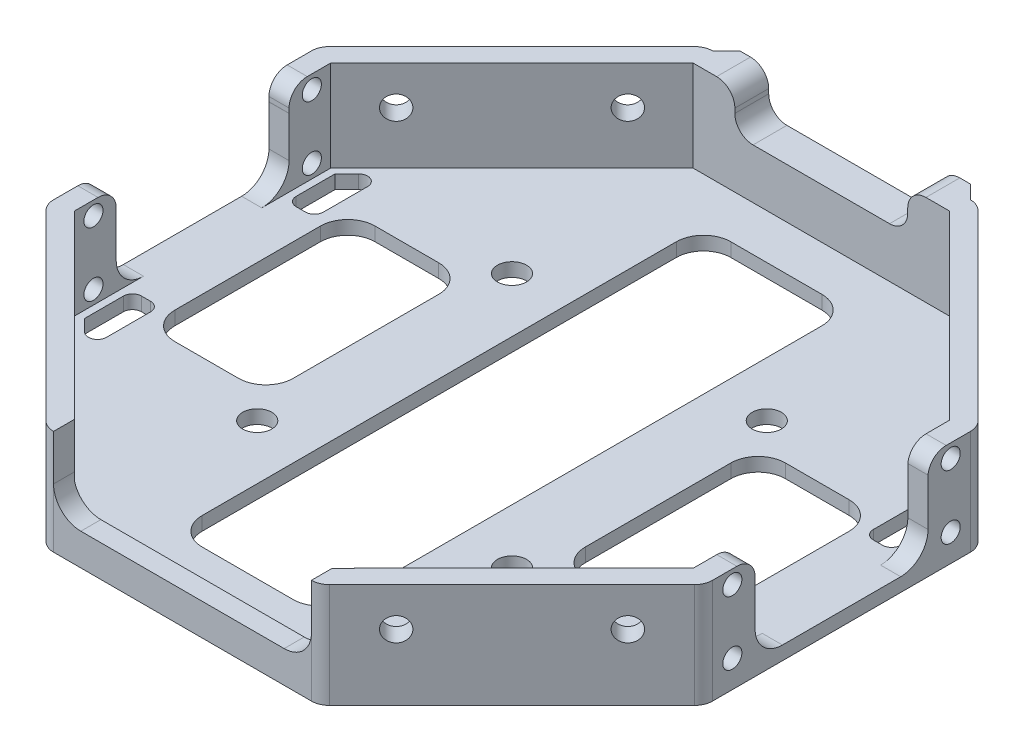
SolidWorks part; units mm, degrees
material "Tough 2000"
ref_plane "Front Plane" through (0, 0, 0) normal (0, 0, 1) x (1, 0, 0)
ref_plane "Top Plane" through (0, 0, 0) normal (0, 1, 0) x (1, 0, 0)
ref_plane "Right Plane" through (0, 0, 0) normal (1, 0, 0) x (0, 0, -1)
sketch "Sketch1" plane through (0, 0, 0) normal (0, 1, 0) x (1, 0, 0)
  line L1 (-11.2132, 40) -> (18.7868, 40)
  line L2 (18.7868, 40) -> (40, 18.7868)
  line L3 (40, 18.7868) -> (40, -11.2132)
  line L5 (-32.4264, 18.7868) -> (-32.4264, -11.2132)
  line L6 (-11.2132, 40) -> (-32.4264, 18.7868)
  line L7 (18.7868, -32.4264) -> (40, -11.2132)
  line L8 (-11.2132, -32.4264) -> (18.7868, -32.4264)
  line L9 (-11.2132, -32.4264) -> (-32.4264, -11.2132)
  point P13 (-32.4264, 3.7868)
  dimension "D1" = 30
  dimension "D2" = 30
  dimension "D3" = 40
  dimension "D4" = 40
extrude "Boss-Extrude1" add sketch "Sketch1" along normal blind 11.5
shell "Shell1" thickness 3 removed face at (3.7868, 11.5, -3.7868)
sketch "Sketch3" plane through (-21.8198, 0, 21.8198) normal (-0.7071, 0, 0.7071) x (0.7071, 0, 0.7071)
  line L0 (0, 11.5) -> (0, 7.25) construction
  line L1 (-15, 11.5) -> (15, 11.5) construction
  line L2 (0, 7.25) -> (9, 7.25) construction
  line L3 (0, 7.25) -> (-9, 7.25) construction
  circle A0 centre (-9, 7.25) radius 1.3
  circle A1 centre (9, 7.25) radius 1.3
extrude "Cut-Extrude1" cut sketch "Sketch3" against normal blind 94
sketch "Sketch4" plane through (-25.6066, 0, -25.6066) normal (-0.7071, 0, -0.7071) x (-0.7071, 0, 0.7071)
  line L0 (-5.3553, 11.5) -> (-5.3553, 7.25) construction
  line L1 (-20.3553, 11.5) -> (9.6447, 11.5) construction
  line L2 (-5.3553, 7.25) -> (-14.3553, 7.25) construction
  line L3 (-5.3553, 7.25) -> (3.6447, 7.25) construction
  circle A0 centre (-14.3553, 7.25) radius 1.3
  circle A1 centre (3.6447, 7.25) radius 1.3
extrude "Cut-Extrude2" cut sketch "Sketch4" against normal blind 94
fillet "Fillet1" radius 2 8 edges at (40, 5.75, 11.2132) (18.7868, 5.75, 32.4264) (40, 5.75, -18.7868) (18.7868, 5.75, -40) (-11.2132, 5.75, -40) (-32.4264, 5.75, -18.7868) (-32.4264, 5.75, 11.2132) (-11.2132, 5.75, 32.4264)
sketch "Sketch5" plane through (0, 0, 32.4264) normal (0, 0, 1) x (1, 0, 0)
  line L0 (3.7868, 11.5) -> (3.7868, 7) construction
  line L1 (-10.3848, 11.5) -> (17.9584, 11.5) construction
  line L2 (3.7868, 7) -> (13.2868, 7)
  line L3 (13.2868, 7) -> (13.2868, 11.5)
  line L4 (3.7868, 7) -> (-5.7132, 7)
  line L5 (-5.7132, 7) -> (-5.7132, 11.5)
  line L6 (-5.7132, 11.5) -> (13.2868, 11.5)
  dimension "D1" = 9.5
extrude "Cut-Extrude3" cut sketch "Sketch5" against normal blind 79
sketch "Sketch6" plane through (-32.4264, 0, 0) normal (-1, 0, 0) x (0, 0, 1)
  line L0 (-3.7868, 11.5) -> (-3.7868, 7) construction
  line L1 (-17.9584, 11.5) -> (10.3848, 11.5) construction
  line L2 (-3.7868, 7) -> (5.7132, 7)
  line L3 (5.7132, 7) -> (5.7132, 11.5)
  line L4 (-3.7868, 7) -> (-13.2868, 7)
  line L5 (-13.2868, 7) -> (-13.2868, 11.5)
  line L6 (-13.2868, 11.5) -> (5.7132, 11.5)
  dimension "D1" = 9.5
extrude "Cut-Extrude4" cut sketch "Sketch6" against normal blind 79
fillet "Fillet2" radius 2 16 edges at (38.5, 11.5, 5.7132) (38.5, 7, 5.7132) (38.5, 11.5, -13.2868) (38.5, 7, -13.2868) (13.2868, 11.5, 30.9264) (13.2868, 7, 30.9264) (-5.7132, 11.5, 30.9264) (-5.7132, 7, 30.9264) (-30.9264, 11.5, -13.2868) (-30.9264, 7, -13.2868) (-30.9264, 11.5, 5.7132) (-30.9264, 7, 5.7132) (13.2868, 11.5, -38.5) (13.2868, 7, -38.5) (-5.7132, 11.5, -38.5) (-5.7132, 7, -38.5)
sketch "Sketch8" plane through (40, 0, 0) normal (1, 0, 0) x (0, 0, -1)
  line L0 (3.7868, 7) -> (-8.2132, 7) construction
  line L1 (11.2868, 7) -> (-3.7132, 7) construction
  line L2 (-8.2132, 7) -> (-8.2132, 10) construction
  line L3 (-8.2132, 7) -> (-8.2132, 3) construction
  line L4 (3.7868, 7) -> (3.7868, 3) construction
  line L5 (15.7868, 7) -> (15.7868, 3) construction
  circle A0 centre (-8.2132, 10) radius 1.05
  circle A1 centre (-8.2132, 3) radius 1.05
  circle A2 centre (15.7868, 3) radius 1.05
  circle A3 centre (15.7868, 10) radius 1.05
extrude "Cut-Extrude7" cut sketch "Sketch8" against normal blind 79
sketch "Sketch10" plane through (0, 3, 0) normal (0, 1, 0) x (1, 0, 0)
  line L0 (17.5442, 37) -> (37, 17.5442)
  line L1 (37, 17.5442) -> (37, -9.9706)
  line L2 (37, -9.9706) -> (17.5442, -29.4264)
  line L3 (17.5442, -29.4264) -> (-9.9706, -29.4264)
  line L4 (-9.9706, -29.4264) -> (-29.4264, -9.9706)
  line L5 (-29.4264, -9.9706) -> (-29.4264, 17.5442)
  line L6 (-29.4264, 17.5442) -> (-9.9706, 37)
  line L7 (-9.9706, 37) -> (17.5442, 37)
extrude "Cut-Extrude8" cut sketch "Sketch10" against normal blind 1.5
sketch "Sketch12" plane through (0, 1.5, 0) normal (0, 1, 0) x (1, 0, 0)
  line L0 (-29.4264, 17.5442) -> (-26.4264, 20.5442)
  line L1 (-29.4264, -3.7132) -> (-29.4264, 11.2868) construction
  line L2 (-29.4264, -5.7132) -> (-29.4264, -3.7132) construction
  line L3 (-29.4264, -4.7132) -> (-26.4264, -4.7132)
  line L4 (-26.4264, -4.7132) -> (-26.4264, -12.9706)
  line L5 (-29.4264, -9.9706) -> (-9.9706, -29.4264) construction
  line L6 (-29.4264, -4.7132) -> (-29.4264, -9.9706)
  line L7 (-29.4264, -9.9706) -> (-26.4264, -12.9706)
  line L8 (3.7868, 37) -> (3.7868, -29.4264)
  line L9 (-3.7132, 37) -> (11.2868, 37) construction
  line L10 (11.2868, -29.4264) -> (-3.7132, -29.4264) construction
  line L11 (-29.4264, 3.7868) -> (37, 3.7868)
  line L12 (37, 11.2868) -> (37, -3.7132) construction
  line L13 (-29.4264, 12.2868) -> (-29.4264, 17.5442)
  line L14 (-26.4264, 12.2868) -> (-26.4264, 20.5442)
  line L15 (-29.4264, 12.2868) -> (-26.4264, 12.2868)
  line L16 (37, -9.9706) -> (34, -12.9706)
  line L17 (37, -4.7132) -> (37, -9.9706)
  line L18 (34, -4.7132) -> (34, -12.9706)
  line L19 (37, -4.7132) -> (34, -4.7132)
  line L20 (37, 12.2868) -> (34, 12.2868)
  line L21 (34, 12.2868) -> (34, 20.5442)
  line L22 (37, 12.2868) -> (37, 17.5442)
  line L23 (37, 17.5442) -> (34, 20.5442)
  line M6 (-9.9706, 37) -> (-29.4264, 17.5442)
  line M7 (-29.4264, 17.5442) -> (-29.4264, -9.9706)
  line M8 (-29.4264, -9.9706) -> (-9.9706, -29.4264)
  line M10 (17.5442, -29.4264) -> (37, -9.9706)
  line M11 (37, -9.9706) -> (37, 17.5442)
  line M12 (37, 17.5442) -> (17.5442, 37)
extrude "Cut-Extrude9" cut sketch "Sketch12" against normal blind 1.5 contours L15 L14 M7 M6 | L4 L3 M7 M8 | L21 L20 M11 M12 | L19 L18 M11 M10 region at (35.389, 1.5, -15.721) region at (35.389, 1.5, 8.1474) region at (-27.8154, 1.5, 8.1474) region at (-27.8154, 1.5, -15.721)
fillet "Fillet3" radius 1 12 edges at (34, 0.75, -12.2868) (34, 0.75, -20.5442) (37, 0.75, -12.2868) (37, 0.75, 4.7132) (34, 0.75, 4.7132) (34, 0.75, 12.9706) (-26.4264, 0.75, 4.7132) (-26.4264, 0.75, 12.9706) (-29.4264, 0.75, 4.7132) (-26.4264, 0.75, -12.2868) (-29.4264, 0.75, -12.2868) (-26.4264, 0.75, -20.5442)
sketch "Sketch13" plane through (0, 1.5, 0) normal (0, 1, 0) x (1, 0, 0)
  line L0 (3.7868, 19.8383) -> (3.7868, -12.2647) construction
  line L1 (19.8383, 3.7868) -> (-12.2647, 3.7868) construction
  line L2 (3.7868, 19.8383) -> (-4.2132, 19.8383)
  line L3 (-4.2132, 19.8383) -> (-4.2132, 32.8383)
  line L4 (-4.2132, 32.8383) -> (2.582, 32.8383)
  line L5 (3.7868, 19.8383) -> (11.7868, 19.8383)
  line L6 (11.7868, 19.8383) -> (11.7868, 32.8383)
  line L7 (11.7868, 32.8383) -> (2.582, 32.8383)
  line L8 (19.8383, -7.2132) -> (19.8383, 14.7868)
  line L9 (19.8383, 14.7868) -> (32.8383, 14.7868)
  line L10 (32.8383, 14.7868) -> (32.8383, -7.2132)
  line L17 (3.7868, -12.2647) -> (-4.2132, -12.2647)
  line L18 (-4.2132, -12.2647) -> (-4.2132, -25.2647)
  line L19 (-4.2132, -25.2647) -> (4.9916, -25.2647)
  line L20 (11.7868, -25.2647) -> (4.9916, -25.2647)
  line L21 (11.7868, -12.2647) -> (11.7868, -25.2647)
  line L22 (3.7868, -12.2647) -> (11.7868, -12.2647)
  line L29 (19.8383, 3.7868) -> (19.8383, 11.7868) [skipped]
  line L30 (19.8383, 11.7868) -> (32.8383, 11.7868) [skipped]
  line L31 (32.8383, 11.7868) -> (32.8383, 4.9916) [skipped]
  line L32 (32.8383, -4.2132) -> (32.8383, 4.9916) [skipped]
  line L33 (19.8383, -4.2132) -> (32.8383, -4.2132) [skipped]
  line L34 (19.8383, 3.7868) -> (19.8383, -4.2132) [skipped]
  line L35 (-12.2647, 3.7868) -> (-12.2647, -4.2132) [skipped]
  line L36 (-12.2647, -4.2132) -> (-25.2647, -4.2132) [skipped]
  line L37 (-25.2647, 11.7868) -> (-25.2647, 2.582) [skipped]
  line L38 (-25.2647, -4.2132) -> (-25.2647, 2.582) [skipped]
  line L39 (-12.2647, 11.7868) -> (-25.2647, 11.7868) [skipped]
  line L40 (-12.2647, 3.7868) -> (-12.2647, 11.7868) [skipped]
  line L41 (19.8383, -7.2132) -> (32.8383, -7.2132)
  line L42 (-12.2647, -7.2132) -> (-25.2647, -7.2132)
  line L43 (-12.2647, 14.7868) -> (-25.2647, 14.7868)
  line L44 (-25.2647, 14.7868) -> (-25.2647, -7.2132)
  line L45 (-12.2647, -7.2132) -> (-12.2647, 14.7868)
  point P11 (32.8383, 3.7868)
  dimension "D1" = 4
  dimension "D2" = 16.0515
extrude "Cut-Extrude10" cut sketch "Sketch13" against normal blind 10
fillet "Fillet4" radius 3 16 edges at (11.7868, 0.75, 12.2647) (-4.2132, 0.75, 12.2647) (-4.2132, 0.75, 25.2647) (11.7868, 0.75, 25.2647) (11.7868, 0.75, -19.8383) (11.7868, 0.75, -32.8383) (-4.2132, 0.75, -19.8383) (-4.2132, 0.75, -32.8383) (19.8383, 0.75, -14.7868) (32.8383, 0.75, -14.7868) (32.8383, 0.75, 7.2132) (19.8383, 0.75, 7.2132) (-25.2647, 0.75, 7.2132) (-12.2647, 0.75, 7.2132) (-25.2647, 0.75, -14.7868) (-12.2647, 0.75, -14.7868)
sketch "Sketch14" plane through (0, 0, 0) normal (0, -1, 0) x (1, 0, 0)
  circle A0 centre (-10.2132, 10.2132) radius 1.6
  circle A1 centre (17.7868, 10.2132) radius 1.6
  circle A2 centre (17.7868, -17.7868) radius 1.6
  circle A3 centre (-10.2132, -17.7868) radius 1.6
extrude "Cut-Extrude12" cut sketch "Sketch14" against normal blind 10
sketch "Sketch15" plane through (0, 0, 0) normal (0, -1, 0) x (-1, 0, 0)
  line L0 (-11.7868, -15.2647) -> (4.2132, -15.2647)
  line L1 (4.2132, -15.2647) -> (4.2132, 22.8383)
  line L2 (4.2132, 22.8383) -> (-11.7868, 22.8383)
  line L3 (-11.7868, 22.8383) -> (-11.7868, -15.2647)
extrude "Cut-Extrude13" cut sketch "Sketch15" against normal blind 10
sketch "Sketch17" plane through (0, 7, 0) normal (0, 1, 0) x (1, 0, 0)
  line L0 (-29.4264, 3.7868) -> (37, 3.7868)
  line L1 (-29.4264, -3.7132) -> (-29.4264, 11.2868) construction
  line L2 (37, 11.2868) -> (37, -3.7132) construction
  line L3 (37.7883, -10.3028) -> (37.7853, 17.8637)
  line L4 (17.8664, 37.7783) -> (-10.3001, 37.7753)
  line L5 (-10.3001, 37.7753) -> (-30.2147, 17.8564)
  line L6 (-30.2147, 17.8564) -> (-30.2117, -10.3101)
  line L7 (-30.2117, -10.3101) -> (-10.2928, -30.2247)
  line L8 (-10.2928, -30.2247) -> (17.8737, -30.2217)
  line L9 (17.8737, -30.2217) -> (37.7883, -10.3028)
  line L10 (37.7853, 17.8637) -> (17.8664, 37.7783)
  circle A0 centre (3.7868, 3.7768) radius 34 construction
  line M1 (-29.4264, -3.7132) -> (-29.4264, 11.2868)
  line M2 (-29.4264, 11.2868) -> (-32.4264, 11.2868)
  line M4 (-32.4264, -3.7132) -> (-29.4264, -3.7132)
extrude "Cut-Extrude15" cut sketch "Sketch17" along normal blind 24 and the other way up to surface (5.5 mm away) contours L3 L10 L4 L5 L6 L7 L8 L9 M2 M1 M4 region at (3.8907, 7, -3.7768) other way up to face at (-10.2132, 1.5, -19.3868)
sketch "Sketch18" plane through (0, 11.5, 0) normal (0, 1, 0) x (1, 0, 0)
  line L0 (-10.3848, -32.4264) -> (17.9584, -32.4264)
  line L1 (17.9584, -32.4264) -> (17.9584, -28.2465)
  line L2 (17.9584, -28.2465) -> (-10.3848, -28.2465)
  line L3 (-10.3848, -28.2465) -> (-10.3848, -32.4264)
extrude "Cut-Extrude16" cut sketch "Sketch18" against normal blind 8
fillet "Fillet5" radius 3 2 edges at (17.9584, 3.5, 31.2817) (-10.3848, 3.5, 31.2796)
sketch "Sketch20" plane through (-30.2128, 0, 0.0032) normal (1, 0, -0.0001) x (-0.0001, 0, -1)
  line L0 (13.29, 9.5) -> (-5.71, 9.5)
  line L1 (-5.71, 9.5) -> (-5.7104, 1.5)
  line L2 (-3.71, 1.5) -> (-10.3069, 1.5) construction
  line L3 (-4.7103, 1.5) -> (-5.7104, 1.5) construction
  line L4 (-5.7104, 1.5) -> (13.2899, 1.5)
  line L5 (13.2899, 1.5) -> (13.29, 9.5)
extrude "Cut-Extrude17" cut sketch "Sketch20" against normal blind 10 and the other way blind 10
sketch "Sketch22" plane through (37.7872, 0, -0.004) normal (-1, 0, 0.0001) x (0.0001, 0, 1)
  line L0 (-13.2899, 1.5) -> (5.7104, 1.5)
  line L1 (5.7104, 1.5) -> (5.7104, 14.8824)
  line L2 (5.7104, 14.8824) -> (-13.2899, 14.8824)
  line L3 (-13.2899, 14.8824) -> (-13.2899, 1.5)
extrude "Cut-Extrude18" cut sketch "Sketch22" against normal blind 10
fillet "Fillet6" radius 3 4 edges at (-31.3203, 1.5, -13.2866) (-31.3193, 1.5, 5.7137) (38.8939, 1.5, 5.7063) (38.8929, 1.5, -13.2941)
sketch "Sketch23" plane through (0, 0, -40) normal (0, 0, -1) x (-1, 0, 0)
  line L0 (-17.9584, 11.5) -> (-17.9584, 0)
  line L1 (-17.9584, 0) -> (10.3848, 0)
  line L2 (10.3848, 0) -> (10.3848, 11.5)
  line L3 (10.3848, 11.5) -> (7.7132, 11.5)
  line L4 (5.7132, 9.5) -> (5.7132, 9)
  line L5 (-13.2868, 9.5) -> (-13.2868, 9)
  line L6 (-11.2868, 7) -> (3.7132, 7)
  line L7 (-17.9584, 11.5) -> (-15.2868, 11.5)
  arc A0 (-13.2868, 9.5) -> (-15.2868, 11.5) centre (-15.2868, 9.5) ccw
  arc A1 (-13.2868, 9) -> (-11.2868, 7) centre (-11.2868, 9) ccw
  arc A2 (3.7132, 7) -> (5.7132, 9) centre (3.7132, 9) ccw
  arc A3 (7.7132, 11.5) -> (5.7132, 9.5) centre (7.7132, 9.5) ccw
extrude "Boss-Extrude2" add sketch "Sketch23" along normal blind 1.5 contours A0 L7 L0 L1 L2 L3 A3 L4 A2 L6 A1 L5
chamfer "Chamfer1" distance 1.5 angle 45 2 edges at (-10.3848, 5.75, -41.5) (17.9584, 5.75, -41.5)
sketch "Sketch24" plane through (0, 0, -41.5) normal (0, 0, -1) x (-1, 0, 0)
  line L0 (-3.7868, 7) -> (-3.7868, 0) construction
  line L1 (-11.2868, 7) -> (3.7132, 7) construction
  line L2 (-16.4584, 0) -> (8.8848, 0) construction
  line L3 (-3.7868, 3.5) -> (4.2132, 3.5)
  circle A0 centre (4.2132, 3.5) radius 3.1
  circle A1 centre (-11.7868, 3.5) radius 3.1
extrude "Cut-Extrude19" cut sketch "Sketch24" against normal blind 3.1 contours A1 | A0 region at (-4.2132, 0.4877, -41.5) region at (11.7868, 3.5, -41.5)
